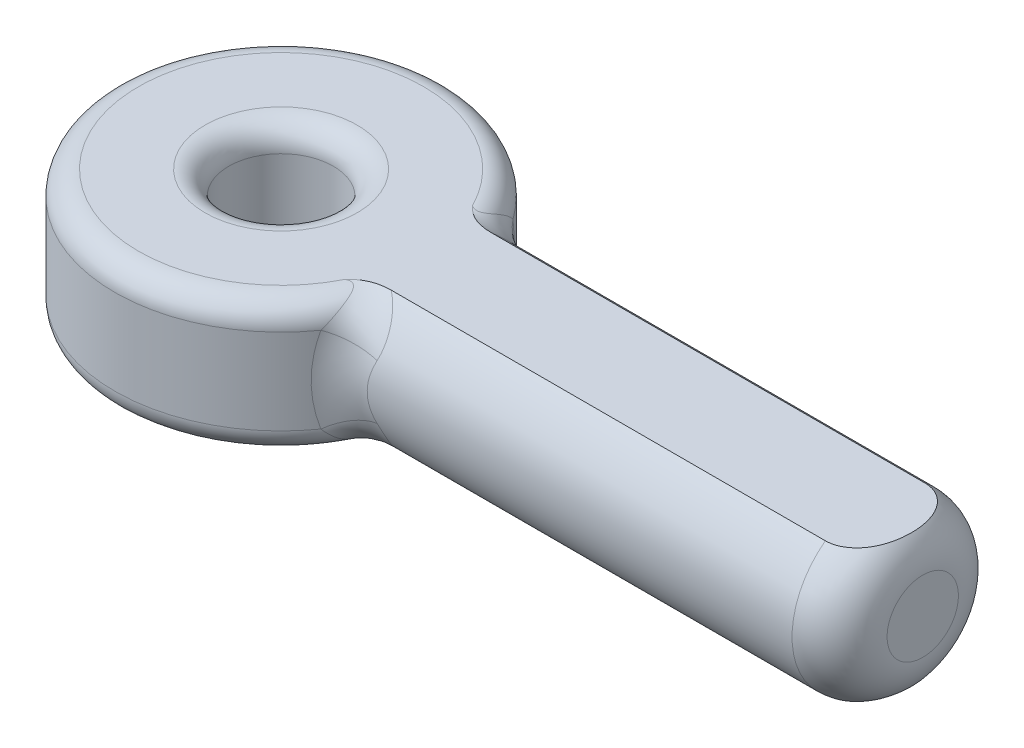
SolidWorks part; units mm, degrees
ref_plane "前视基准面" through (0, 0, 0) normal (0, 0, 1) x (1, 0, 0)
ref_plane "上视基准面" through (0, 0, 0) normal (0, 1, 0) x (1, 0, 0)
ref_plane "右视基准面" through (0, 0, 0) normal (1, 0, 0) x (0, 0, -1)
sketch "草图1" plane through (0, 0, 0) normal (0, 1, 0) x (1, 0, 0)
  circle A0 centre (0, 0) radius 1.1
  circle A1 centre (0, 0) radius 3.5
  dimension "D1" = 2.2
  dimension "D2" = 7
extrude "凸台-拉伸1" add sketch "草图1" along normal mid plane 2.8
ref_plane "基准面1" through (3.5, 0, 0) normal (1, 0, 0) x (0, 0, -1)
fillet "圆角1" radius 0.5 2 edges at (0, -1.4, 3.5) (0, 1.4, 3.5)
sketch "草图3" plane through (3.5, 0, 0) normal (1, 0, 0) x (0, 0, -1)
  line L0 (-1.05, 1.4) -> (1.05, 1.4)
  line L1 (1.1, 1.4) -> (-1.1, 1.4) construction
  line L2 (-1.05, -1.4) -> (1.05, -1.4)
  arc A0 (1.05, -1.4) -> (1.05, 1.4) centre (0, 0) ccw
  arc A1 (-1.05, 1.4) -> (-1.05, -1.4) centre (0, 0) ccw
  dimension "D1" = 3.5
extrude "凸台-拉伸2" add sketch "草图3" along normal blind 10 and the other way blind 1
fillet "圆角2" radius 1 6 edges at (3.1141, 1.2665, -1.2077) (3.1142, -1.2664, -1.2078) (3.1141, -1.2665, 1.2077) (3.1142, 1.2664, 1.2078) (3.0368, 0.1869, 1.74) (3.056, -0.3891, 1.7062)
fillet "圆角3" radius 1 1 edges at (13.5, 0, 1.75)
fillet "圆角4" radius 0.5 2 edges at (0, -1.4, 1.1) (0, 1.4, 1.1)
